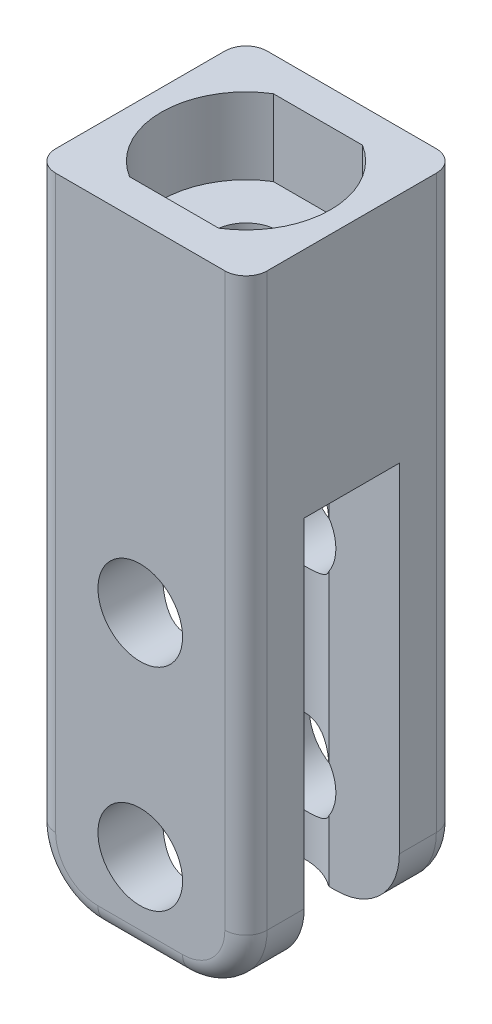
SolidWorks part; units mm, degrees
ref_plane "Front Plane" through (0, 0, 0) normal (0, 0, 1) x (1, 0, 0)
ref_plane "Top Plane" through (0, 0, 0) normal (0, 1, 0) x (1, 0, 0)
ref_plane "Right Plane" through (0, 0, 0) normal (1, 0, 0) x (0, 0, -1)
ref_axis "X Axis" through (-88.99, 0, 0) along (1, 0, 0)
ref_axis "Y Axiz" through (0, 0, 55) along (0, 0, -1)
ref_axis "Z Axis" through (0, 55, 0) along (0, -1, 0)
sketch "Sketch2" plane through (0, 0, 0) normal (0, 1, 0) x (1, 0, 0)
  line L1 (-5, -5) -> (5, -5)
  line L2 (-5, -5) -> (-5, 5)
  line L3 (-5, 5) -> (5, 5)
  line L4 (5, -5) -> (5, 5)
  line L5 (-5, -5) -> (5, 5) construction
  line L6 (-5, 5) -> (5, -5) construction
  point P0 (0, 0)
  dimension "D1" = 10
extrude "Boss-Extrude3" add sketch "Sketch2" along normal blind 30
sketch "Sketch1" plane through (0, 0, 5) normal (0, 0, 1) x (1, 0, 0)
  line L2 (0, 2.8079) -> (0, 4) construction
  line L3 (0, -5.5) -> (0, 5.5) construction
  line L5 (0, 55) -> (0, -55) construction
  line L6 (5.5, 0) -> (-5.5, 0) construction
  circle A0 centre (0, 4) radius 2
  circle A4 centre (0, 14) radius 2
  dimension "D1" = 4
  dimension "D3" = 4
  dimension "D2" = 10
extrude "Cut-Extrude1" cut sketch "Sketch1" against normal through all
sketch "Sketch3" plane through (0, 0, 0) normal (1, 0, 0) x (0, 0, -1)
  line L0 (0, 4.95) -> (0, -4.95) construction
  line L1 (-2.25, 19) -> (2.25, 19)
  line L2 (-2.25, 19) -> (-2.25, 0)
  line L3 (-2.25, 0) -> (2.25, 0)
  line L4 (2.25, 19) -> (2.25, 0)
  line L5 (-2.25, 19) -> (2.25, 0) construction
  line L6 (-2.25, 0) -> (2.25, 19) construction
  line L7 (4.95, 0) -> (-4.95, 0) construction
  point P0 (0, 9.5)
  dimension "D1" = 19
  dimension "D2" = 4.5
extrude "Cut-Extrude2" cut sketch "Sketch3" against normal through all and the other way through all
sketch "Sketch5" plane through (0, 30, 0) normal (0, 1, 0) x (1, 0, 0)
  line L0 (-2.1071, -3.4) -> (2.1071, -3.4)
  line L2 (2.1071, 3.4) -> (-2.1071, 3.4)
  circle A0 centre (0, 0) radius 1.5
  arc A1 (-2.1071, 3.4) -> (-2.1071, -3.4) centre (0, 0) ccw
  arc A2 (2.1071, -3.4) -> (2.1071, 3.4) centre (0, 0) ccw
  dimension "D1" = 3
  dimension "D2" = 8
  dimension "D3" = 6.8
extrude "Cut-Extrude3" cut sketch "Sketch5" against normal blind 3.6
extrude "Cut-Extrude4" cut sketch "Sketch5<2>" against normal through all contours A0 region at (0, 30, 0)
sketch "Sketch5<2>" plane through (0, 30, 0) normal (0, 1, 0) x (1, 0, 0) same geometry as "Sketch5"
fillet "Fillet3" radius 3 4 edges at (-5, 0, -3.625) (5, 0, -3.625) (5, 0, 3.625) (-5, 0, 3.625)
fillet "Fillet1" radius 1 10 edges at (5, 16.5, 5) (-5, 16.5, -5) (5, 16.5, -5) (-5, 16.5, 5) (0, 0, -5) (0, 0, 5) (-4.1213, 0.8787, -5) (4.1213, 0.8787, -5) (4.1213, 0.8787, 5) (-4.1213, 0.8787, 5)
sketch "Sketch6" plane through (0, 19, 0) normal (0, -1, 0) x (1, 0, 0)
  circle A0 centre (0, 0) radius 2.8
  dimension "D1" = 5.6
extrude "Cut-Extrude5" cut sketch "Sketch6" along normal through all and the other way blind 3.25
